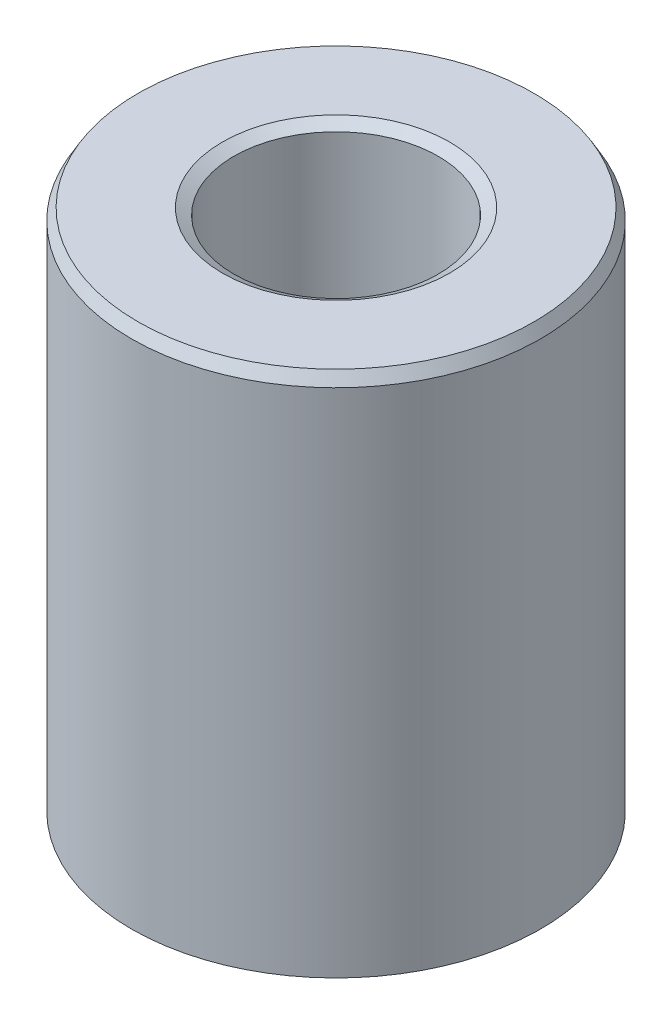
SolidWorks part; units mm, degrees
ref_plane "Front Plane" through (0, 0, 0) normal (0, 0, 1) x (1, 0, 0)
ref_plane "Top Plane" through (0, 0, 0) normal (0, 1, 0) x (1, 0, 0)
ref_plane "Right Plane" through (0, 0, 0) normal (1, 0, 0) x (0, 0, -1)
sketch "Sketch1" plane through (0, 0, 0) normal (0, 1, 0) x (1, 0, 0)
  circle A0 centre (0, 0) radius 57.5
  dimension "SLEEVE_OD" = 115
extrude "Boss-Extrude1" add sketch "Sketch1" along normal blind 148.7345
sketch "Sketch2" plane through (0, 0, 0) normal (0, 1, 0) x (1, 0, 0)
  circle A0 centre (0, 0) radius 28.7232
  dimension "BORE_D" = 57.4465
extrude "Cut-Extrude1" cut sketch "Sketch2" along normal through all
chamfer "Chamfer1" distance 3.2099 angle 30 4 edges at (0, 148.7345, 28.7232) (0, 0, 28.7232) (0, 0, 57.5) (0, 148.7345, 57.5) first distance on face at (0, 148.7345, 28.7232) first distance on face at (0, 0, 28.7232) first distance on face at (0, 148.7345, 57.5)
